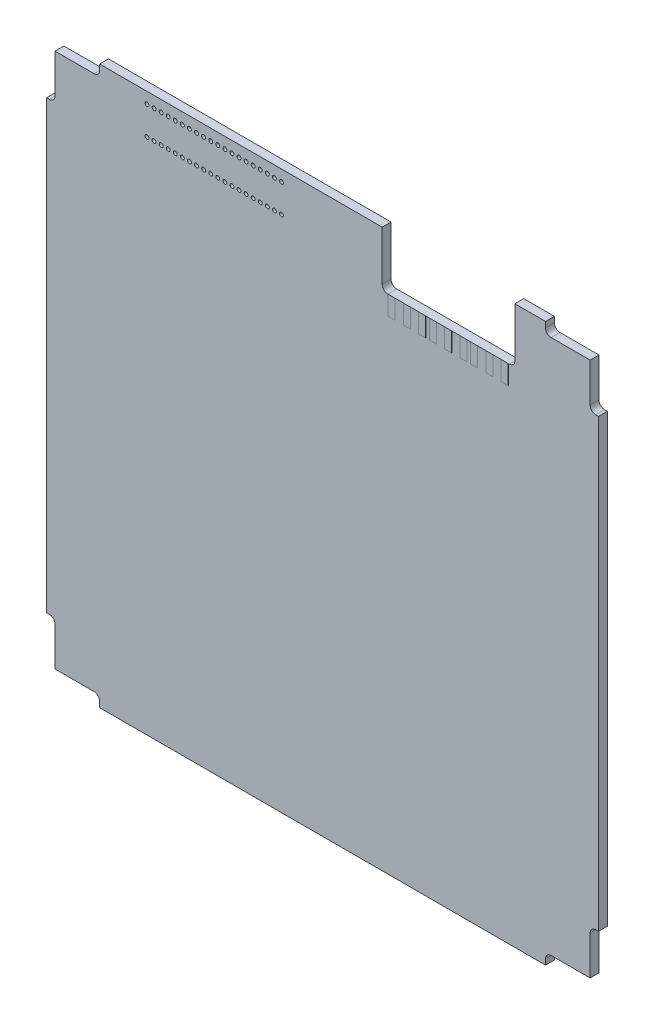
SolidWorks part; units mm, degrees
material "ABS"
ref_plane "Front Plane" through (0, 0, 0) normal (0, 0, 1) x (1, 0, 0)
ref_plane "Top Plane" through (0, 0, 0) normal (0, 1, 0) x (1, 0, 0)
ref_plane "Right Plane" through (0, 0, 0) normal (1, 0, 0) x (0, 0, -1)
sketch "Sketch1" plane through (0, 0, 0) normal (0, 0, 1) x (1, 0, 0)
  line L0 (-40, 50) -> (-40, 48)
  line L1 (-50, -50) -> (50, -50)
  line L2 (-50, -50) -> (-50, 50)
  line L3 (-50, 50) -> (50, 50)
  line L4 (50, -50) -> (50, 50)
  line L5 (-50, -50) -> (50, 50) construction
  line L6 (-50, 50) -> (50, -50) construction
  line L7 (-50, 50) -> (-40, 50)
  line L8 (-50, 50) -> (-50, 40)
  line L9 (-40, 48) -> (-48, 48)
  line L10 (-48, 48) -> (-48, 40)
  line L11 (50, 50) -> (40, 50)
  line L12 (50, 50) -> (50, 40)
  line L13 (-48, 40) -> (-50, 40)
  line L14 (50, 40) -> (48, 40)
  line L15 (-50, -50) -> (-37.8649, -50)
  line L16 (-50, -50) -> (-50, -37.8649)
  line L17 (50, 50) -> (50, 40)
  line L18 (50, 50) -> (40, 50)
  line L19 (50, -50) -> (41.5, -50)
  line L20 (50, -50) -> (50, -41.5)
  line L21 (48, 40) -> (48, 48)
  line L22 (48, 48) -> (40, 48)
  line L23 (40, 48) -> (40, 50)
  line L24 (40, -50) -> (40, -48)
  line L25 (50, -50) -> (40, -50)
  line L26 (50, -50) -> (50, -40)
  line L27 (40, -48) -> (48, -48)
  line L28 (48, -48) -> (48, -40)
  line L29 (48, -40) -> (50, -40)
  line L30 (-50, -40) -> (-48, -40)
  line L31 (-50, -50) -> (-50, -40)
  line L32 (-50, -50) -> (-40, -50)
  line L33 (-48, -40) -> (-48, -48)
  line L34 (-48, -48) -> (-40, -48)
  line L35 (-40, -48) -> (-40, -50)
  point P0 (0, 0)
  point P38 (0, 0)
  dimension "D1" = 100
  dimension "D2" = 100
  dimension "D3" = 2
  dimension "D4" = 10
  dimension "D5" = 4
extrude "Boss-Extrude1" add sketch "Sketch1" along normal blind 1.5875 contours L1 L4 L3 L2 region at (0, 0, 0)
fillet "Fillet1" radius 1 8 edges at (-48, -40, 0.7937) (-40, -48, 0.7937) (40, -48, 0.7937) (48, -40, 0.7937) (48, 40, 0.7937) (40, 48, 0.7937) (-40, 48, 0.7937) (-48, 40, 0.7937)
sketch "Sketch2" plane through (0, 0, 1.5875) normal (0, 0, 1) x (1, 0, 0)
  line L0 (0, 50) -> (0, -50) construction
  line L1 (-40, 50) -> (40, 50) construction
  line L2 (-40, -50) -> (40, -50) construction
  line L3 (-50, -40) -> (-50, 40) construction
  line L4 (-40, 50) -> (40, 50) construction
  circle A0 centre (-31.5, 48) radius 0.35
  circle A1 centre (-30.23, 48) radius 0.35
  circle A2 centre (-28.96, 48) radius 0.35
  circle A3 centre (-27.69, 48) radius 0.35
  circle A4 centre (-26.42, 48) radius 0.35
  circle A5 centre (-25.15, 48) radius 0.35
  circle A6 centre (-23.88, 48) radius 0.35
  circle A7 centre (-22.61, 48) radius 0.35
  circle A8 centre (-21.34, 48) radius 0.35
  circle A9 centre (-20.07, 48) radius 0.35
  circle A10 centre (-18.8, 48) radius 0.35
  circle A11 centre (-17.53, 48) radius 0.35
  circle A12 centre (-16.26, 48) radius 0.35
  circle A13 centre (-14.99, 48) radius 0.35
  circle A14 centre (-13.72, 48) radius 0.35
  circle A15 centre (-12.45, 48) radius 0.35
  circle A16 centre (-11.18, 48) radius 0.35
  circle A17 centre (-9.91, 48) radius 0.35
  circle A18 centre (-8.64, 48) radius 0.35
  circle A19 centre (-7.37, 48) radius 0.35
  circle A20 centre (-30.23, 42.92) radius 0.35
  circle A21 centre (-28.96, 42.92) radius 0.35
  circle A22 centre (-27.69, 42.92) radius 0.35
  circle A23 centre (-26.42, 42.92) radius 0.35
  circle A24 centre (-25.15, 42.92) radius 0.35
  circle A25 centre (-23.88, 42.92) radius 0.35
  circle A26 centre (-22.61, 42.92) radius 0.35
  circle A27 centre (-21.34, 42.92) radius 0.35
  circle A28 centre (-20.07, 42.92) radius 0.35
  circle A29 centre (-18.8, 42.92) radius 0.35
  circle A30 centre (-17.53, 42.92) radius 0.35
  circle A31 centre (-16.26, 42.92) radius 0.35
  circle A32 centre (-14.99, 42.92) radius 0.35
  circle A33 centre (-13.72, 42.92) radius 0.35
  circle A34 centre (-12.45, 42.92) radius 0.35
  circle A35 centre (-11.18, 42.92) radius 0.35
  circle A36 centre (-9.91, 42.92) radius 0.35
  circle A37 centre (-8.64, 42.92) radius 0.35
  circle A38 centre (-7.37, 42.92) radius 0.35
  circle A39 centre (-31.5, 42.92) radius 0.35
  dimension "D1" = 0.7
  dimension "D4" = 18.5
  dimension "D5" = 2
  dimension "D2" = 5.08
  dimension "D3" = 1.27
extrude "Cut-Extrude1" cut sketch "Sketch2" against normal through all
sketch "Sketch3" plane through (0, 50, 0) normal (0, 1, 0) x (1, 0, 0)
  line L0 (-40, 0) -> (40, 0) construction
  line L1 (10.7, 0) -> (19.7, 0)
  line L2 (10.7, 0) -> (10.7, -1.5875)
  line L3 (10.7, -1.5875) -> (19.7, -1.5875)
  line L4 (-40, -1.5875) -> (-40, 0) construction
  line L5 (-40, -1.5875) -> (40, -1.5875) construction
  line L6 (15.2, 0) -> (15.2, -1.5875) construction
  line L7 (12, 0) -> (12, -1.5875) construction
  line L8 (18.4, 0) -> (18.4, -1.5875) construction
  line L9 (-40, -1.5875) -> (40, -1.5875) construction
  line L12 (19.7, 0) -> (34.5, 0)
  line L14 (19.7, -1.5875) -> (34.5, -1.5875)
  line L15 (34.5, 0) -> (34.5, -1.5875)
  dimension "D1" = 9
  dimension "D2" = 6.4
  dimension "D3" = 3.2
  dimension "D5" = 14.8
  dimension "D6" = 50.7
extrude "Cut-Extrude2" cut sketch "Sketch3" against normal blind 9.8806
fillet "Fillet2" radius 1 2 edges at (10.7, 40.1194, 0.7938) (34.5, 40.1194, 0.7937)
sketch "Sketch5" plane through (0, 0, 0) normal (0, 0, -1) x (-1, 0, 0)
  line L0 (40, -50) -> (-40, -50) construction
  line L1 (-49.5, 50) -> (49.5, 50)
  line L2 (-49.5, 50) -> (-49.5, -50)
  line L3 (-49.5, -50) -> (49.5, -50)
  line L4 (49.5, 50) -> (49.5, -50)
  line L5 (40, 50) -> (-10.7, 50) construction
  line L6 (50, -40) -> (50, 40) construction
  dimension "D1" = 99
  dimension "D2" = 0.5
extrude "Cut-Extrude3" cut sketch "Sketch5" against normal through all flip side to cut
sketch "Sketch6" plane through (0, 0, 1.5875) normal (0, 0, 1) x (1, 0, 0)
  line L0 (12.4, 40.1194) -> (12.4, 36.6894) construction
  line L1 (11.765, 40.1194) -> (13.035, 40.1194)
  line L2 (11.765, 40.1194) -> (11.765, 36.6894)
  line L3 (11.765, 36.6894) -> (13.035, 36.6894)
  line L4 (13.035, 40.1194) -> (13.035, 36.6894)
  line L5 (14.505, 40.1194) -> (15.775, 40.1194)
  line L6 (14.505, 40.1194) -> (14.505, 36.6894)
  line L7 (14.505, 36.6894) -> (15.775, 36.6894)
  line L8 (15.775, 40.1194) -> (15.775, 36.6894)
  line L9 (17.245, 40.1194) -> (18.515, 40.1194)
  line L10 (17.245, 40.1194) -> (17.245, 36.6894)
  line L11 (17.245, 36.6894) -> (18.515, 36.6894)
  line L12 (18.515, 40.1194) -> (18.515, 36.6894)
  line L13 (15.14, 40.1194) -> (15.14, 36.6894) construction
  line L14 (17.88, 40.1194) -> (17.88, 36.6894) construction
  line L15 (11.7, 40.1194) -> (33.5, 40.1194) construction
  line L16 (12.8, 36.9194) -> (12, 36.9194) construction
  line L17 (19.165, 40.1194) -> (20.435, 40.1194)
  line L18 (19.165, 40.1194) -> (19.165, 36.6894)
  line L19 (19.165, 36.6894) -> (20.435, 36.6894)
  line L20 (20.435, 40.1194) -> (20.435, 36.6894)
  line L21 (21.905, 40.1194) -> (23.175, 40.1194)
  line L22 (21.905, 40.1194) -> (21.905, 36.6894)
  line L23 (21.905, 36.6894) -> (23.175, 36.6894)
  line L24 (23.175, 40.1194) -> (23.175, 36.6894)
  line L25 (24.645, 40.1194) -> (25.915, 40.1194)
  line L26 (24.645, 40.1194) -> (24.645, 36.6894)
  line L27 (24.645, 36.6894) -> (25.915, 36.6894)
  line L28 (25.915, 40.1194) -> (25.915, 36.6894)
  line L29 (19.8, 40.1194) -> (19.8, 36.6894) construction
  line L30 (22.54, 40.1194) -> (22.54, 36.6894) construction
  line L31 (25.28, 40.1194) -> (25.28, 36.6894) construction
  line L32 (26.565, 40.1194) -> (27.835, 40.1194)
  line L33 (26.565, 40.1194) -> (26.565, 36.6894)
  line L34 (26.565, 36.6894) -> (27.835, 36.6894)
  line L35 (27.835, 40.1194) -> (27.835, 36.6894)
  line L36 (29.305, 40.1194) -> (30.575, 40.1194)
  line L37 (29.305, 40.1194) -> (29.305, 36.6894)
  line L38 (29.305, 36.6894) -> (30.575, 36.6894)
  line L39 (30.575, 40.1194) -> (30.575, 36.6894)
  line L40 (32.045, 40.1194) -> (33.315, 40.1194)
  line L41 (32.045, 40.1194) -> (32.045, 36.6894)
  line L42 (32.045, 36.6894) -> (33.315, 36.6894)
  line L43 (33.315, 40.1194) -> (33.315, 36.6894)
  line L44 (27.2, 40.1194) -> (27.2, 36.6894) construction
  line L45 (29.94, 40.1194) -> (29.94, 36.6894) construction
  line L46 (32.68, 40.1194) -> (32.68, 36.6894) construction
  point P20 (12.4, 36.9194)
  point P42 (19.8, 36.9194)
  point P61 (27.2, 36.9194)
  dimension "D1" = 1.27
  dimension "D2" = 3.43
  dimension "D3" = 2.74
  dimension "D4" = 2.74
  dimension "D6" = 7.4
  dimension "D5" = 3
extrude "Boss-Extrude2" add sketch "Sketch6" along normal blind 0.01
sketch "Sketch7" plane through (0, 0, 1.5875) normal (0, 0, 1) x (1, 0, 0)
  line L0 (-40, 50) -> (-36.5, 50)
  line L1 (-40, 50) -> (10.7, 50) construction
  line L2 (-36.5, 50) -> (-36.5, 48)
  line L3 (-36.5, 48) -> (-41.5, 48)
  line L4 (-41, 48) -> (-48, 48) construction
  line L5 (-41.5, 48) -> (-41.5, 41.5)
  line L6 (-41.5, 41.5) -> (-42, 41.5)
  line L7 (-47, 36.5) -> (-47, -36.5)
  line L8 (-40, 50) -> (-49.5, 50)
  line L9 (-49.5, 50) -> (-49.5, -50)
  line L10 (-49.5, -40) -> (-49.5, 40) construction
  line L11 (0, 0) -> (-49.5, 0) construction
  line L12 (-40, -50) -> (-49.5, -50)
  line L13 (-41.5, -41.5) -> (-42, -41.5)
  line L14 (-41.5, -48) -> (-41.5, -41.5)
  line L15 (-36.5, -48) -> (-41.5, -48)
  line L16 (-36.5, -50) -> (-36.5, -48)
  line L17 (-40, -50) -> (-36.5, -50)
  arc A0 (-42, 41.5) -> (-47, 36.5) centre (-42, 36.5) ccw
  arc A1 (-42, -41.5) -> (-47, -36.5) centre (-42, -36.5) cw
  point P25 (-47, 0)
  dimension "D1" = 5
  dimension "D2" = 13
  dimension "D3" = 8
  dimension "D4" = 8.5
  dimension "D5" = 2.5
  dimension "D6" = 5
